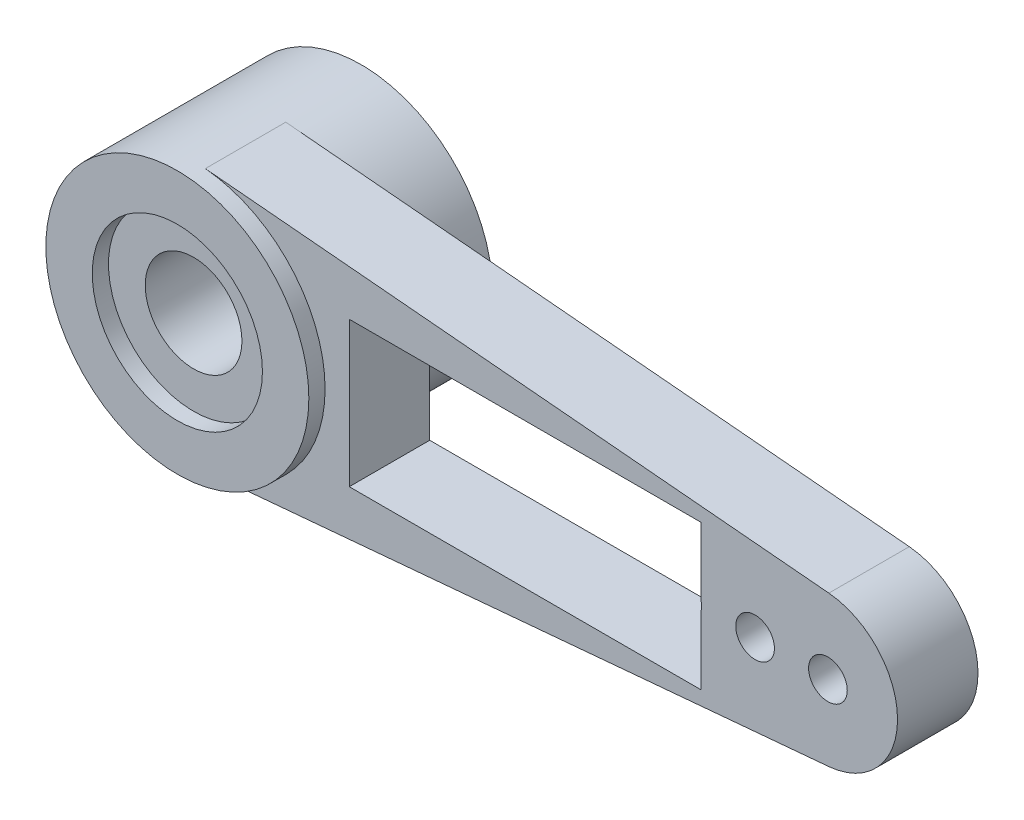
SolidWorks part; units mm, degrees
ref_plane "Front Plane" through (0, 0, 0) normal (0, 0, 1) x (1, 0, 0)
ref_plane "Top Plane" through (0, 0, 0) normal (0, 1, 0) x (1, 0, 0)
ref_plane "Right Plane" through (0, 0, 0) normal (1, 0, 0) x (0, 0, -1)
sketch "Sketch1" plane through (0, 0, 0) normal (0, 0, 1) x (1, 0, 0)
  line L0 (18.2, -5.1547) -> (18.2, 5.1547) construction
  line L1 (-3.4, -4.0329) -> (-3.4, 4.0329) construction
  line L2 (16.424, 1.9422) -> (0.3034, 3.3864)
  line L3 (16.424, -1.9422) -> (0.3034, -3.3864)
  line L4 (16.9, 0.7754) -> (16.9, -0.9477) construction
  circle A0 centre (0, 0) radius 3.4
  arc A1 (16.424, -1.9422) -> (16.424, 1.9422) centre (16.25, 0) ccw
  circle A2 centre (5.1, 0) radius 0.5
  circle A9 centre (6.9833, 0) radius 0.5
  circle A10 centre (8.8667, 0) radius 0.5
  circle A11 centre (10.75, 0) radius 0.5
  circle A12 centre (12.6333, 0) radius 0.5
  circle A13 centre (14.5167, 0) radius 0.5
  circle A14 centre (16.4, 0) radius 0.5
  circle A15 centre (0, 0) radius 2.2
  circle A16 centre (0, 0) radius 1.25
  point P5 (18.2, 0)
  point P8 (-3.4, 0)
  dimension "D1" = 6.8
  dimension "D3" = 3.9
  dimension "D4" = 7
  dimension "D6" = 1
  dimension "D9" = 2.5
  dimension "D2" = 21.6
  dimension "D5" = 1.3
  dimension "D7" = 11.3
  dimension "D8" = 1.2
extrude "Base" add sketch "Sketch1" along normal blind 2.08 contours L3 A1 L2 A0 A14 A13 A12 A11 A10 A9 A2 | A0 A15 | A15 A16 region at (9.5091, 0, 0) region at (2.4382, 2.2295, 0) region at (-2.1378, 0, 0)
extrude "Connection" add sketch "Sketch1<3>" along normal blind 2.5 and the other way blind 2.25 contours A0 A15 region at (2.4382, 2.2295, 0)
sketch "Sketch1<3>" plane through (0, 0, 0) normal (0, 0, 1) x (1, 0, 0) same geometry as "Sketch1"
sketch "Sketch2" plane through (0, 0, 0) normal (0, 0, -1) x (-1, 0, 0)
  line L0 (0, 0) -> (-21.2401, 0) construction
  line L2 (-4.025, -1.875) -> (-13.125, -1.875)
  line L3 (-4.025, -1.875) -> (-4.025, 1.875)
  line L4 (-4.025, 1.875) -> (-13.125, 1.875)
  line L5 (-13.125, -1.875) -> (-13.125, 1.875)
  line L6 (-4.025, -1.875) -> (-13.125, 1.875) construction
  line L7 (-4.025, 1.875) -> (-13.125, -1.875) construction
  point P4 (-8.575, 0)
  dimension "D1" = 9.1
  dimension "D2" = 3.75
  dimension "D3" = 8.575
extrude "Alignment channel" cut sketch "Sketch2" against normal blind 10
